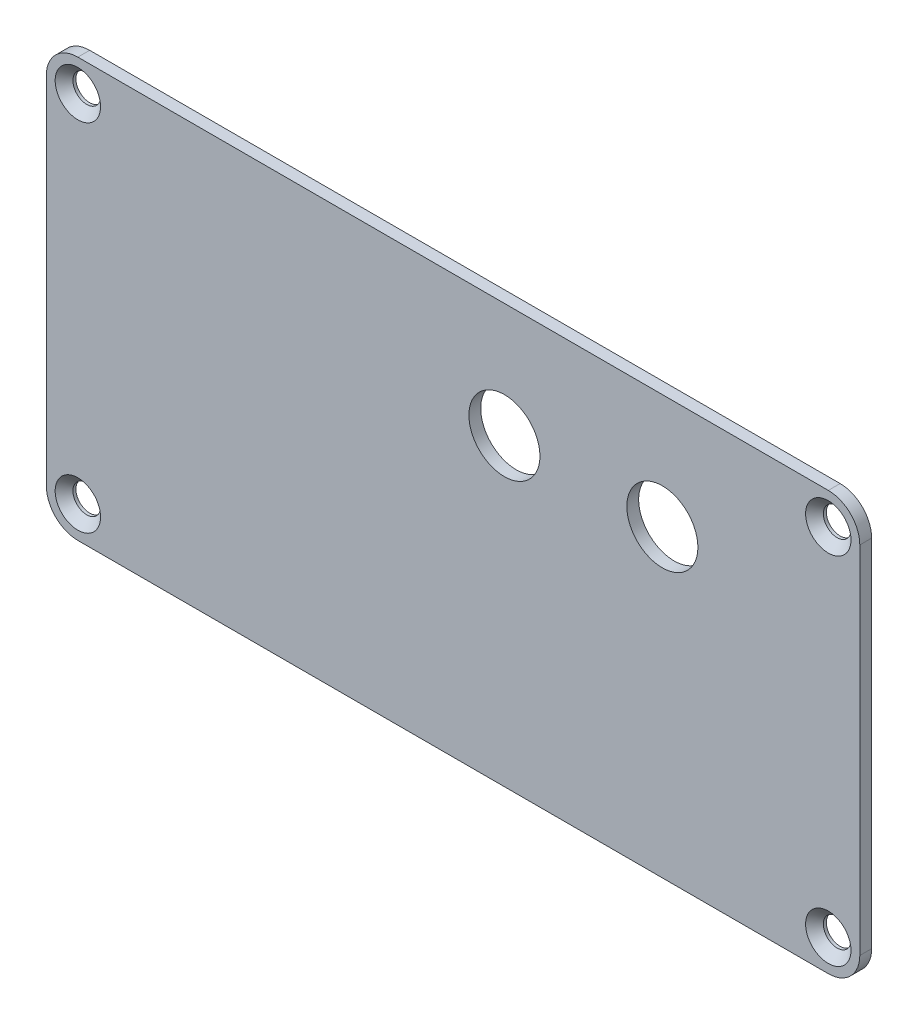
SolidWorks part; units mm, degrees
ref_plane "Plan de face" through (0, 0, 0) normal (0, 0, 1) x (1, 0, 0)
ref_plane "Plan de dessus" through (0, 0, 0) normal (0, 1, 0) x (1, 0, 0)
ref_plane "Plan de droite" through (0, 0, 0) normal (1, 0, 0) x (0, 0, -1)
ref_plane "Plan1" through (0, 0, -0.75) normal (0, 0, -1) x (-1, 0, 0)
sketch "Esquisse1" plane through (0, 0, -0.75) normal (0, 0, -1) x (-1, 0, 0)
  line L0 (-51.5, -26.5) -> (51.5, -26.5)
  line L1 (51.5, -26.5) -> (51.5, 26.5)
  line L2 (51.5, 26.5) -> (-51.5, 26.5)
  line L3 (-51.5, 26.5) -> (-51.5, -26.5)
extrude "Boss.-Extru.1" add sketch "Esquisse1" against normal blind 1.5
hole_wizard "Fraisage pour vis à tête fraisée M31" positions "Esquisse3" profile "Esquisse2" countersink size "M3" standard "Ansi Metric"
sketch "Esquisse3" plane through (0, 0, 0.75) normal (0, 0, 1) x (1, 0, 0)
  point P0 (-47.51, 22.5)
  point P1 (47.51, 22.5)
  point P2 (47.51, -22.5)
  point P3 (-47.51, -22.5)
sketch "Esquisse2" plane through (-47.51, 22.5, 0.75) normal (1, 0, 0) x (0, -1, 0)
  line L0 (0, 0) -> (0, 1.5)
  line L1 (0, 1.5) -> (1.75, 1.5)
  line L2 (1.75, 1.5) -> (1.75, 1.125)
  line L3 (1.75, 1.125) -> (2.875, 0)
  line L5 (2.875, 0) -> (0, 0)
  line L6 (-1.75, 1.125) -> (-2.875, 0) construction
  line L11 (0, -6.35) -> (0, 107.95) construction
  dimension "Diamètre du perçage jusqu'au prochain" = 3.5
  dimension "Profondeur du perçage jusqu'au prochain" = 1.5
  dimension "Diamètre du fraisage entrant" = 5.75
  dimension "Angle du fraisage entrant" = 90
fillet "Congé1" radius 3.99 4 edges at (51.5, 26.5, 0) (51.5, -26.5, 0) (-51.5, 26.5, 0) (-51.5, -26.5, 0) tangent propagation no
sketch "Esquisse4" plane through (0, 0, 0.75) normal (0, 0, 1) x (1, 0, 0)
  line L0 (0, -26.5) -> (0, 26.5) construction
  line L1 (47.51, -26.5) -> (-47.51, -26.5) construction
  line L2 (-47.51, 26.5) -> (47.51, 26.5) construction
  line L3 (-51.5, 0) -> (51.5, 0) construction
  line L6 (-51.5, -22.51) -> (-51.5, 22.51) construction
  line L7 (51.5, 22.51) -> (51.5, -22.51) construction
  circle A0 centre (26.5, 12) radius 4.5
  circle A1 centre (6.5, 12) radius 4.5
  dimension "D1" = 9
  dimension "D3" = 12
  dimension "D2" = 25
  dimension "D4" = 20
extrude "Enlèv. mat.-Extru.1" cut sketch "Esquisse4" against normal through all
